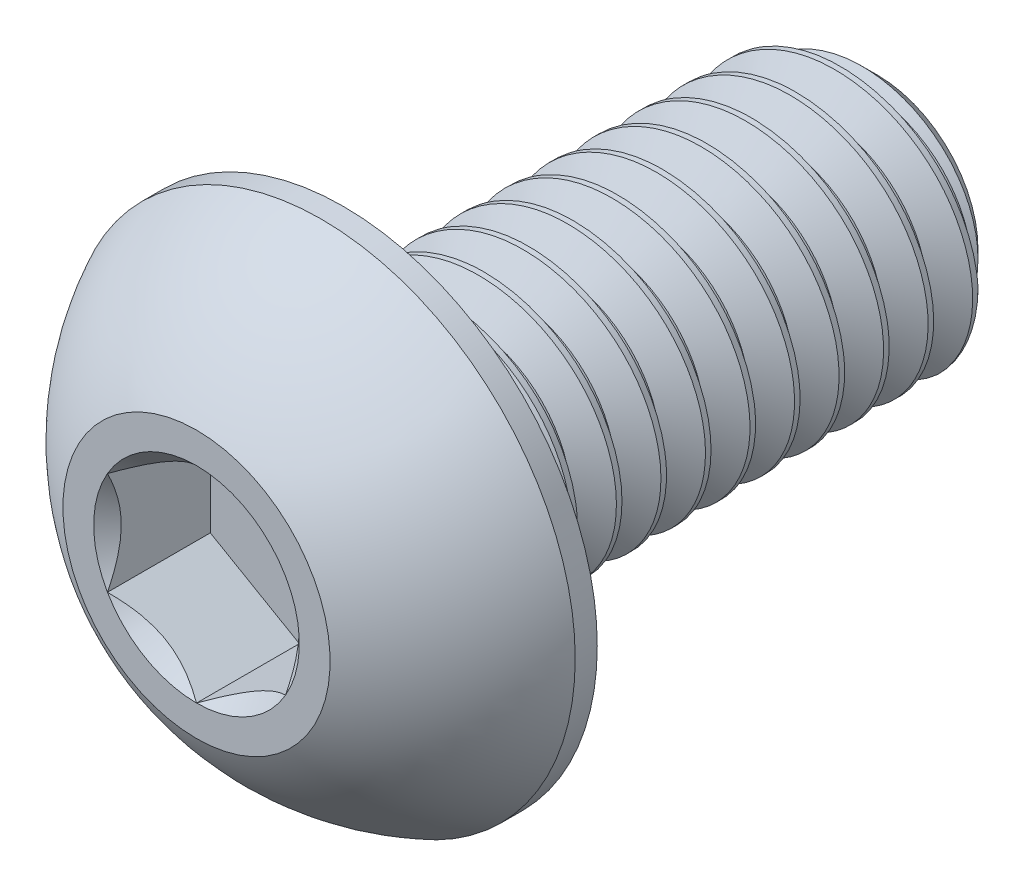
SolidWorks part; units mm, degrees
material "AISI 304"
ref_plane "Front" through (0, 0, 0) normal (0, 0, 1) x (1, 0, 0)
ref_plane "Top" through (0, 0, 0) normal (0, 1, 0) x (1, 0, 0)
ref_plane "Right" through (0, 0, 0) normal (1, 0, 0) x (0, 0, -1)
sketch "Sketch1" plane through (0, 0, 0) normal (1, 0, 0) x (0, 0, -1)
  line L2 (1.65, 1.5) -> (7.65, 1.5)
  line L3 (7.65, 1.5) -> (7.65, 0)
  line L4 (7.65, 0) -> (1.65, 0)
  line L6 (1.4025, 2.85) -> (1.65, 2.85) construction
  line L7 (7.65, 1.5) -> (7.65, -1.5) construction
  line L8 (0, 0) -> (1.65, 0) construction
  line L9 (1.65, 2.85) -> (1.65, -2.85) construction
  line L11 (1.65, 1.5) -> (1.65, 0)
  line L13 (0, 1) -> (0, -1) construction
  line L14 (0, 1) -> (0, 1.5) construction
  arc A3 (0, 1.5) -> (1.4025, 2.85) centre (2.7948, 0) cw construction
  dimension "D1" = 0.2475
  dimension "Head Ht" = 1.65
  dimension "Head Dia" = 5.7
  dimension "Dia" = 3
  dimension "Lg" = 6
  dimension "Hex" = 2
revolve "Revolve1" add sketch "Sketch1" angle 360 mid plane about L4
sketch "Sketch3" plane through (0, 0, -7.65) normal (0, 0, -1) x (-1, 0, 0)
  circle A0 centre (0, 0) radius 1.5
curve "Helix/Spiral1" pitch 0.5 height 6.5 radius 1.5 centre (0, 0, -7.65) axis (0, 0, 1) start towards (0, 1, 0)
sketch "Sketch2" plane through (0, 0, 0) normal (1, 0, 0) x (0, 0, -1)
  line L0 (7.65, 1.5) -> (8.0875, 1.5)
  line L1 (8.0875, 1.5) -> (7.9, 1.1752)
  line L2 (7.9, 1.1752) -> (7.8375, 1.1752)
  line L3 (7.8375, 1.1752) -> (7.65, 1.5)
  line L4 (7.7438, 1.3376) -> (7.9938, 1.3376) construction
  dimension "D1" = 60
  dimension "D2" = 0.0625
  dimension "D3" = 0.25
chamfer "Chamfer1" distance 0.375 angle 45 1 edges at (0, 1.5, -7.65)
sweep "Cut-Sweep1" cut profiles "Sketch2" path "Helix/Spiral1" align with end faces yes
sketch "Sketch7" plane through (0, 0, 0) normal (1, 0, 0) x (0, 0, -1)
  line L6 (1.4025, 2.85) -> (1.65, 2.85) construction
  line L8 (0, 0) -> (1.65, 0) construction
  line L11 (1.65, 2.85) -> (1.65, -2.85) construction
  line L12 (1.4025, 2.85) -> (1.65, 2.85)
  line L13 (0, 0) -> (1.65, 0)
  line L14 (0, 1) -> (0, -1) construction
  line L15 (1.65, 2.85) -> (1.65, 0)
  line L16 (0, 1.5) -> (0, 0)
  arc A2 (1.4025, 2.85) -> (0, 1.5) centre (2.7948, 0) ccw construction
  arc A3 (1.4025, 2.85) -> (0, 1.5) centre (2.7948, 0) ccw
revolve "Revolve2" add sketch "Sketch7" angle 360 mid plane about L13
sketch "Sketch5" plane through (0, 0, 0) normal (0, 0, 1) x (1, 0, 0)
  line L1 (1, -0.5774) -> (1, 0.5774)
  line L2 (1, 0.5774) -> (0, 1.1547)
  line L3 (0, 1.1547) -> (-1, 0.5774)
  line L4 (-1, 0.5774) -> (-1, -0.5774)
  line L5 (-1, -0.5774) -> (0, -1.1547)
  line L6 (0, -1.1547) -> (1, -0.5774)
  circle A0 centre (0, 0) radius 1 construction
extrude "Cut-Extrude2" cut sketch "Sketch5" against normal blind 1.155
sketch "Sketch6" plane through (0, 0, 0) normal (0, 0, 1) x (1, 0, 0)
  circle A0 centre (0, 0) radius 1.1547
extrude "Cut-Extrude3" cut sketch "Sketch6" against normal blind 1.155 draft 45
sketch "Sketch9" [suppressed] plane through (0, 0, -4.2164) normal (0, 0, 1) x (1, 0, 0)
  circle A2 centre (0, 0) radius 3.9687
extrude "Boss-Extrude2" [suppressed] add sketch "Sketch9" against normal offset from surface (9.525 mm away) 28.575 up to face at (0, 1.125, -7.65)
sketch "Sketch10" plane through (0, 0, 0) normal (1, 0, 0) x (0, 0, -1)
  line L0 (7.65, 1.5) -> (7.65, -1.5) construction
  point P0 (6.9, -1.5)
  dimension "D1" = 0.75
equation "\"D3@Helix/Spiral1\" = \"Lg@Sketch1\" + \"D4@Helix/Spiral1\""
equation "\"D2@Sketch2\" = \"D4@Helix/Spiral1\" * .125"
equation "\"D3@Sketch2\" = \"D4@Helix/Spiral1\" * .5"
equation "\"D1@Chamfer1\" = \"D4@Helix/Spiral1\" * .75"
equation "\"D1@Cut-Extrude2\" = \"Head Ht@Sketch1\" * .7"
equation "\"D1@Sketch1\" = \"Head Ht@Sketch1\" * .15"
equation "\"D1@Sketch10\" = \"D4@Helix/Spiral1\" * 1.5"
equation "\"D1@Cut-Extrude3\" = \"D1@Cut-Extrude2\""
